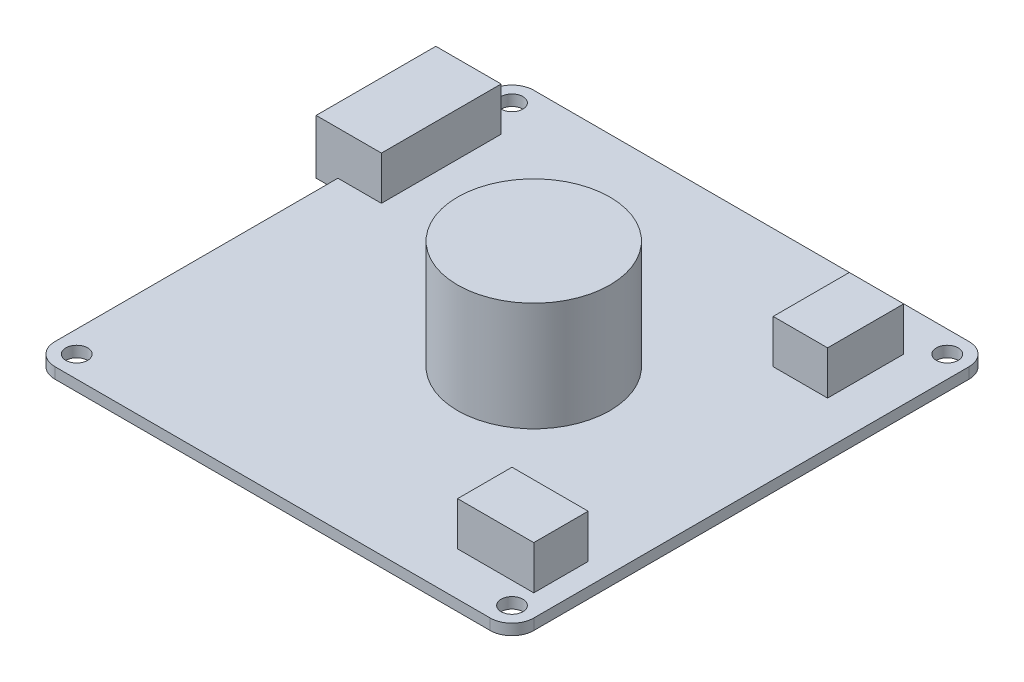
SolidWorks part; units mm, degrees
ref_plane "Front Plane" through (0, 0, 0) normal (0, 0, 1) x (1, 0, 0)
ref_plane "Top Plane" through (0, 0, 0) normal (0, 1, 0) x (1, 0, 0)
ref_plane "Right Plane" through (0, 0, 0) normal (1, 0, 0) x (0, 0, -1)
sketch "Sketch1" plane through (0, 0, 0) normal (0, 1, 0) x (1, 0, 0)
  line L1 (-20, -22) -> (20, -22)
  line L2 (-22, -20) -> (-22, 20)
  line L3 (-20, 22) -> (20, 22)
  line L4 (22, -20) -> (22, 20)
  line L5 (-22, -22) -> (22, 22) construction
  line L6 (-22, 22) -> (22, -22) construction
  line L7 (-24, 17) -> (-18, 17)
  line L8 (-24, 17) -> (-24, 6)
  line L9 (-24, 6) -> (-18, 6)
  line L10 (-18, 17) -> (-18, 6)
  line L11 (13, 18) -> (18, 18)
  line L12 (13, 18) -> (13, 11)
  line L13 (13, 11) -> (18, 11)
  line L14 (18, 18) -> (18, 11)
  line L15 (13, -13) -> (20, -13)
  line L16 (13, -13) -> (13, -18)
  line L17 (13, -18) -> (20, -18)
  line L18 (20, -13) -> (20, -18)
  circle A0 centre (2, 0) radius 7
  arc A1 (20, -22) -> (22, -20) centre (20, -20) ccw
  arc A2 (20, 22) -> (22, 20) centre (20, 20) cw
  arc A3 (-22, 20) -> (-20, 22) centre (-20, 20) cw
  arc A4 (-20, -22) -> (-22, -20) centre (-20, -20) cw
  circle A5 centre (-20, 20) radius 1
  circle A6 centre (20, 20) radius 1
  circle A7 centre (20, -20) radius 1
  circle A8 centre (-20, -20) radius 1
  point P0 (5.295, -0.6669)
  point P36 (9.1508, -1.3623)
  point P37 (0, 0)
  point P39 (22, 0)
  dimension "D3" = 14
  dimension "D4" = 2
  dimension "D5" = 2
  dimension "D6" = 2
  dimension "D7" = 2
  dimension "D8" = 2
  dimension "D9" = 2
  dimension "D10" = 2
  dimension "D11" = 2
  dimension "D1" = 44
  dimension "D2" = 44
  dimension "D12" = 11
  dimension "D13" = 6
  dimension "D14" = 2
  dimension "D15" = 5
  dimension "D16" = 7
  dimension "D17" = 5
  dimension "D18" = 7
  dimension "D19" = 5
  dimension "D20" = 4
  dimension "D21" = 4
  dimension "D22" = 2
  dimension "D23" = 4
  dimension "D24" = 24
extrude "Boss-Extrude1" add sketch "Sketch1" along normal blind 1 contours A4 L1 A1 L4 A2 L3 A3 L2 L7 L10 L9 A8 A7 A6 A5 A0 L11 L14 L13 L12 L15 L18 L17 L16 region at (-20.9742, 0, 20.9742)
extrude "Boss-Extrude2" add sketch "Sketch1<3>" along normal blind 11 contours A0 region at (2, 0, 0)
sketch "Sketch1<3>" plane through (0, 0, 0) normal (0, 1, 0) x (1, 0, 0) same geometry as "Sketch1"
extrude "Boss-Extrude3" add sketch "Sketch1<4>" along normal blind 5 contours L10 L7 L2 L9 | L8 L9 L2 L7 | L14 L11 L12 L13 | L18 L15 L16 L17 region at (-23, 0, -11.5) region at (-20, 0, -11.5) region at (15.5, 0, -14.5) region at (16.5, 0, 15.5)
sketch "Sketch1<4>" plane through (0, 0, 0) normal (0, 1, 0) x (1, 0, 0) same geometry as "Sketch1"
